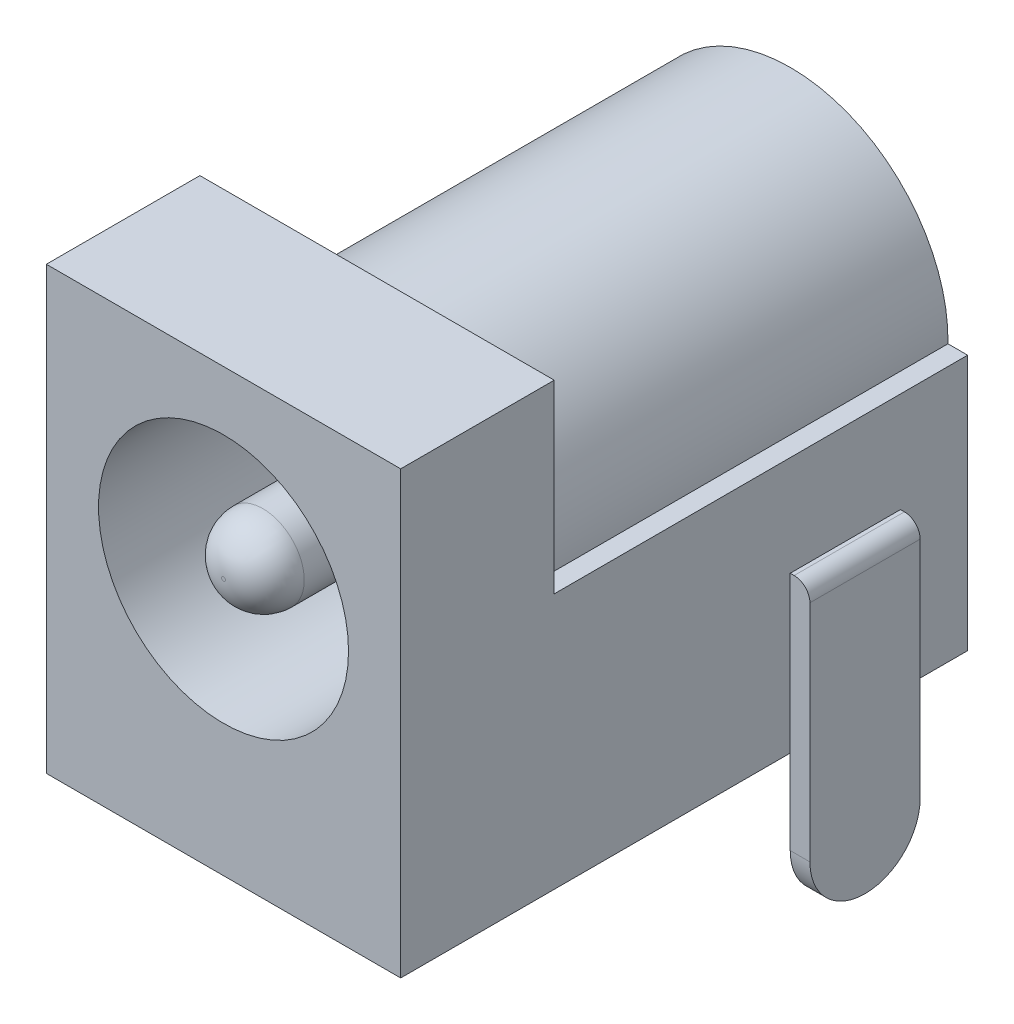
SolidWorks part; units mm, degrees
ref_plane "Piano frontale" through (0, 0, 0) normal (0, 0, 1) x (1, 0, 0)
ref_plane "Piano superiore" through (0, 0, 0) normal (0, 1, 0) x (1, 0, 0)
ref_plane "Piano destro" through (0, 0, 0) normal (1, 0, 0) x (0, 0, -1)
sketch "Schizzo1" plane through (0, 0, 0) normal (0, 1, 0) x (1, 0, 0)
  line L1 (0, 0) -> (9, 0)
  line L2 (0, 0) -> (0, 14.4)
  line L3 (0, 14.4) -> (9, 14.4)
  line L4 (9, 0) -> (9, 14.4)
  dimension "D1" = 14.4
  dimension "D2" = 9
extrude "Estrusione-Estrusione1" add sketch "Schizzo1" along normal blind 11.2
sketch "Schizzo2" plane through (0, 0, 0) normal (0, 0, 1) x (1, 0, 0)
  line L0 (4.5, 11.2) -> (4.5, 0) construction
  line L1 (0, 11.2) -> (9, 11.2) construction
  line L2 (0, 0) -> (9, 0) construction
  circle A0 centre (4.5, 6.525) radius 3.175
  dimension "D1" = 4.675
extrude "Taglio-Estrusione1" cut sketch "Schizzo2" against normal blind 10
sketch "Schizzo3" plane through (0, 0, -10) normal (0, 0, 1) x (1, 0, 0)
  circle A0 centre (4.5, 6.525) radius 1.05
extrude "Estrusione-Estrusione2" add sketch "Schizzo3" along normal blind 10
fillet "Raccordo1" radius 1 1 edges at (5.55, 6.525, 0)
sketch "Schizzo4" plane through (0, 0, -14.4) normal (0, 0, -1) x (-1, 0, 0)
  line L0 (-9, 6.5) -> (-9, 11.2)
  line L1 (-9, 11.2) -> (-9, 0) construction
  line L2 (-9, 11.2) -> (0, 11.2)
  line L3 (0, 11.2) -> (0, 6.5)
  line L4 (0, 11.2) -> (0, 0) construction
  line L5 (-9, 0) -> (0, 0) construction
  line L6 (-9, 6.5) -> (-8.5, 6.5)
  line L7 (0, 6.5) -> (-0.5, 6.5)
  arc A0 (-8.5, 6.5) -> (-0.5, 6.5) centre (-4.5, 6.5774) cw
  dimension "D1" = 6.5
  dimension "D2" = 6.5
  dimension "D3" = 0.5
  dimension "D4" = 0.5
extrude "Taglio-Estrusione2" cut sketch "Schizzo4" against normal blind 10.5
sketch "Schizzo5" plane through (0, 0, 0) normal (0, -1, 0) x (-1, 0, 0)
  line L0 (-4.5, 0) -> (-4.5, 14.4) construction
  line L1 (-3.1, 8.5) -> (-5.9, 8.5)
  line L2 (-3.1, 8.5) -> (-3.1, 9)
  line L3 (-3.1, 9) -> (-5.9, 9)
  line L4 (-5.9, 8.5) -> (-5.9, 9)
  line L6 (0, 0) -> (-9, 0) construction
  line L7 (-9, 14.4) -> (0, 14.4) construction
  line L8 (-3.1, 13.5) -> (-5.9, 13.5)
  line L9 (-3.1, 13.5) -> (-3.1, 14)
  line L10 (-3.1, 14) -> (-5.9, 14)
  line L11 (-5.9, 13.5) -> (-5.9, 14)
  line L13 (-9.0435, 9.85) -> (-9.5435, 9.85)
  line L14 (-9.0435, 9.85) -> (-9.0435, 12.65)
  line L15 (-9.0435, 12.65) -> (-9.5435, 12.65)
  line L16 (-9.5435, 9.85) -> (-9.5435, 12.65)
  dimension "D1" = 0.5
  dimension "D2" = 2.8
  dimension "D3" = 1.4
  dimension "D4" = 0.5
  dimension "D5" = 2.8
  dimension "D6" = 1.4
  dimension "D7" = 4.5
  dimension "D8" = 8.5
  dimension "D9" = 2.8
  dimension "D10" = 0.5
  dimension "D11" = 0.85
extrude "Estrusione-Estrusione3" add sketch "Schizzo5" along normal blind 3.5 and the other way blind 4
fillet "Raccordo2" radius 0.4 1 edges at (9.5435, 4, -11.25)
fillet "Raccordo3" radius 1.4 2 edges at (9.2935, -3.5, -9.85) (9.2935, -3.5, -12.65)
fillet "Raccordo4" radius 1.4 2 edges at (3.1, -3.5, -13.75) (5.9, -3.5, -13.75)
fillet "Raccordo5" radius 1.4 2 edges at (3.1, -3.5, -8.75) (5.9, -3.5, -8.75)
